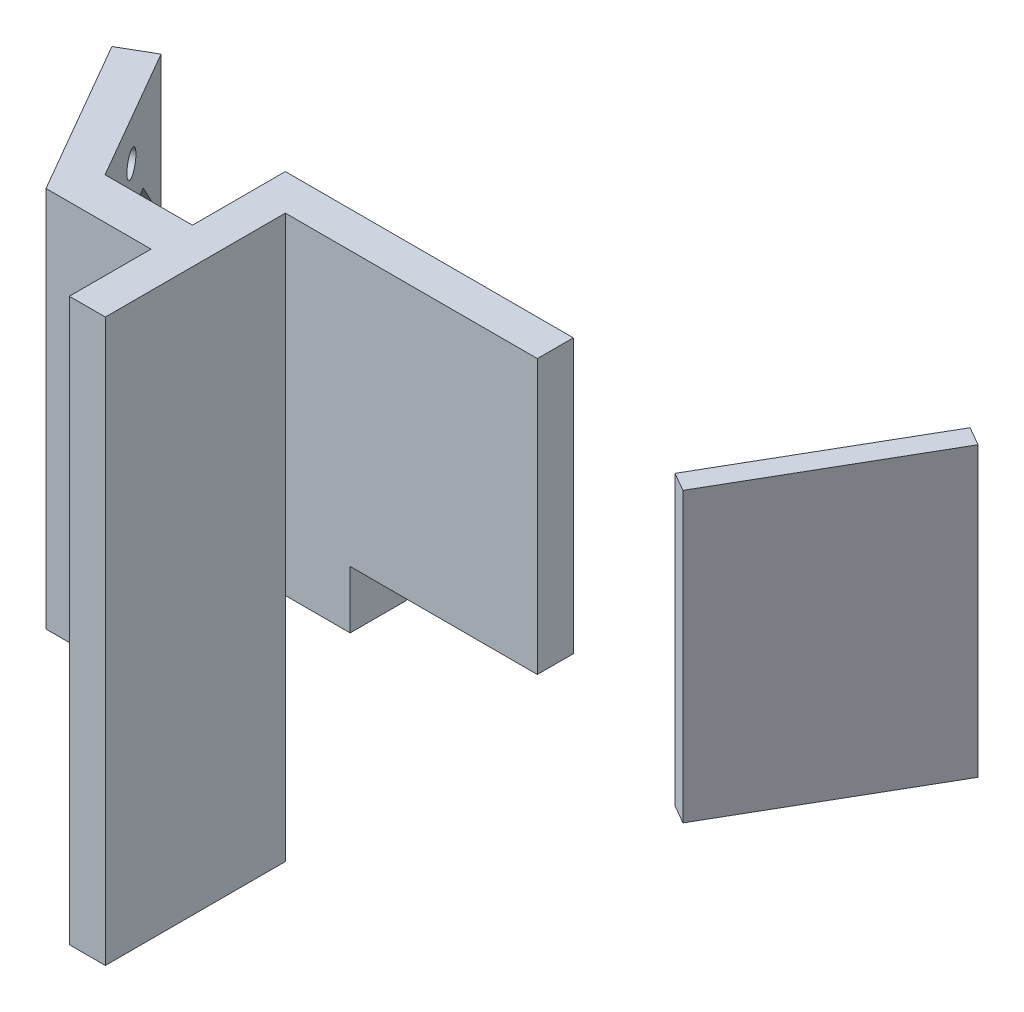
SolidWorks part; units mm, degrees
ref_plane "Front Plane" through (0, 0, 0) normal (0, 0, 1) x (1, 0, 0)
ref_plane "Top Plane" through (0, 0, 0) normal (0, 1, 0) x (1, 0, 0)
ref_plane "Right Plane" through (0, 0, 0) normal (1, 0, 0) x (0, 0, -1)
sketch "Sketch1" plane through (0, 0, 0) normal (0, 1, 0) x (1, 0, 0)
  line L5 (-30.5, -23.25) -> (9.5, -23.25)
  line L6 (-30.5, -23.25) -> (-30.5, -28.25)
  line L7 (-30.5, -28.25) -> (9.5, -28.25)
  line L8 (9.5, -23.25) -> (9.5, -28.25)
  dimension "D1" = 28.25
  dimension "D2" = 30.5
  dimension "D3" = 40
  dimension "D4" = 5
extrude "Boss-Extrude1" add sketch "Sketch1" against normal blind 38 contours L6 L5 L8 L7
sketch "Sketch2" plane through (0, 0, 0) normal (0, 1, 0) x (1, 0, 0)
  line L5 (-30.5, -28.25) -> (-25.5, -28.25)
  line L6 (-30.5, -28.25) -> (-30.5, -53.25)
  line L7 (-30.5, -53.25) -> (-25.5, -53.25)
  line L8 (-25.5, -28.25) -> (-25.5, -53.25)
  dimension "D3" = 5
  dimension "D4" = 25
extrude "Boss-Extrude2" add sketch "Sketch2" against normal blind 78
sketch "Sketch3" plane through (0, 0, 0) normal (0, 1, 0) x (1, 0, 0)
  line L0 (0, 0) -> (-84.2707, 0) construction
  line L1 (0, 0) -> (81.3022, 0) construction
  line L2 (0, 0) -> (-72.1856, -41.6764) construction
  line L3 (0, 0) -> (60.952, -35.1907) construction
  line L4 (-51.9615, -30) -> (-66.7386, -4.4053) construction
  line L5 (51.9615, -30) -> (65.7414, -6.1326) construction
  dimension "D1" = 30
  dimension "D2" = 30
  dimension "D3" = 60
  dimension "D4" = 60
ref_plane "Plane1" through (-51.9615, 0, 30) normal (0.866, 0, -0.5) x (-0.5, 0, -0.866)
ref_plane "Plane2" through (51.9615, 0, 30) normal (0.866, 0, 0.5) x (0.5, 0, -0.866)
sketch "Sketch4" plane through (-51.9615, 0, 30) normal (0.866, 0, -0.5) x (-0.5, 0, -0.866)
  line L0 (1.25, -53) -> (8.25, -43.003)
  line L1 (11.25, 0) -> (-13.75, 0)
  line L2 (11.25, 0) -> (11.25, -37)
  line L3 (1.25, -53) -> (-13.75, -53)
  line L4 (-13.75, 0) -> (-13.75, -53)
  line L5 (11.25, -37) -> (8.25, -37)
  line L6 (8.25, -37) -> (8.25, -43.003)
  dimension "D1" = 53
  dimension "D2" = 25
  dimension "D3" = 13.75
  dimension "D4" = 0
  dimension "D5" = 55
  dimension "D6" = 10
  dimension "D7" = 3
  dimension "D8" = 16
extrude "Boss-Extrude3" add sketch "Sketch4" along normal blind 5 separate body
sketch "Sketch5" plane through (51.9615, 0, 30) normal (0.866, 0, 0.5) x (0.5, 0, -0.866)
  line L1 (-15, 9) -> (15, 9)
  line L2 (-15, 9) -> (-15, -31)
  line L3 (-15, -31) -> (15, -31)
  line L4 (15, 9) -> (15, -31)
  dimension "D1" = 30
  dimension "D2" = 40
  dimension "D3" = 15
  dimension "D4" = 9
extrude "Boss-Extrude4" add sketch "Sketch5" against normal blind 3 separate body
sketch "Sketch9" plane through (0, 0, 28.25) normal (0, 0, -1) x (-1, 0, 0)
  line L0 (30.5, -38) -> (25.5, -38) construction
  line L1 (36.5, -38) -> (16.5, -38)
  line L2 (36.5, -38) -> (36.5, -46)
  line L3 (36.5, -46) -> (16.5, -46)
  line L4 (16.5, -38) -> (16.5, -46)
  line L5 (30.5, -78) -> (30.5, -38) construction
  dimension "D1" = 0
  dimension "D2" = 14
  dimension "D3" = 20
  dimension "D4" = 8
extrude "Boss-Extrude7" add sketch "Sketch9" along normal blind 7.8
sketch "Sketch6" plane through (-51.9615, 0, 30) normal (-0.866, 0, 0.5) x (0.5, 0, 0.866)
  line L0 (-11.25, -37) -> (-11.25, 0) construction
  line L1 (-10, -11.5) -> (10, -11.5)
  line L2 (-10, -11.5) -> (-10, -39.5)
  line L3 (-10, -39.5) -> (10, -39.5)
  line L4 (10, -11.5) -> (10, -39.5)
  line L5 (13.75, -53) -> (-1.25, -53) construction
  line L6 (-11.25, 0) -> (13.75, 0) construction
  line L7 (-4.5, -11.5) -> (-10, -18.0546)
  line L9 (-4.5, -39.5) -> (-10, -32.9454)
  circle A0 centre (0, -5.5) radius 1.7
  circle A1 centre (0, -45.5) radius 1.7
  point P10 (-10, -25.5)
  point P16 (0, 0)
  dimension "D1" = 3.4
  dimension "D2" = 3.4
  dimension "D7" = 11.25
  dimension "D8" = 11.25
  dimension "D9" = 40
  dimension "D10" = 5.5
  dimension "D3" = 28
  dimension "D4" = 20
  dimension "D5" = 1.25
  dimension "D6" = 27.5
  dimension "D11" = 50
  dimension "D12" = 5.5
  dimension "D13" = 50
  dimension "D14" = 5.5
extrude "Cut-Extrude1" cut sketch "Sketch6" against normal through all contours L9 L3 L4 L1 L7 L2 | A0 region at (-51.6806, -25.5, 30.4866)
extrude "Cut-Extrude2" cut sketch "Sketch6<3>" against normal blind 7.8 contours A1 region at (-51.9615, -45.5, 30)
sketch "Sketch6<3>" plane through (-51.9615, 0, 30) normal (-0.866, 0, 0.5) x (0.5, 0, 0.866) same geometry as "Sketch6"
sketch "Sketch7" plane through (0, 0, 0) normal (0, 1, 0) x (1, 0, 0)
  line L0 (-45.0865, -41.9078) -> (-30.5, -41.9078)
  line L1 (-30.5, -23.25) -> (-30.5, -53.25) construction
  line L2 (-42.6314, -36.1603) -> (-30.5, -36.1603)
  line L3 (-53.2564, -17.7572) -> (-40.7564, -39.4078) construction
  line L4 (-30.5, -36.1603) -> (-30.5, -41.9078)
  line L5 (-42.6314, -36.1603) -> (-40.7564, -39.4078)
  line L6 (-40.7564, -39.4078) -> (-45.0865, -41.9078)
  dimension "D1" = 0
extrude "Boss-Extrude5" add sketch "Sketch7" against normal up to surface (53 mm away) contours L6 L0 L4 L2 L5 up to face at (-46.6715, -53, 34.1627)
hole_wizard "M3 Clearance Hole1" positions "3DSketch1" profile "Sketch10" hole size "M3" standard "ISO" end condition through all
sketch3d "3DSketch1"
  line L0 (-32.25, -81, 24.25) -> (-32.25, -78, 24.25) construction
  point P0 (-32.25, -81, 24.25)
sketch "Sketch10" plane through (-32.25, -81, 24.25) normal (1, 0, 0) x (0, 0, -1)
  line L0 (0, 0) -> (0, 90)
  line L1 (0, 90) -> (1.7, 90)
  line L2 (1.7, 90) -> (1.7, 0)
  line L5 (1.7, 0) -> (0, 0)
  line L11 (0, -6.35) -> (0, 107.95) construction
  dimension "Thru Hole Dia." = 3.4
  dimension "Thru Hole Depth" = 90
